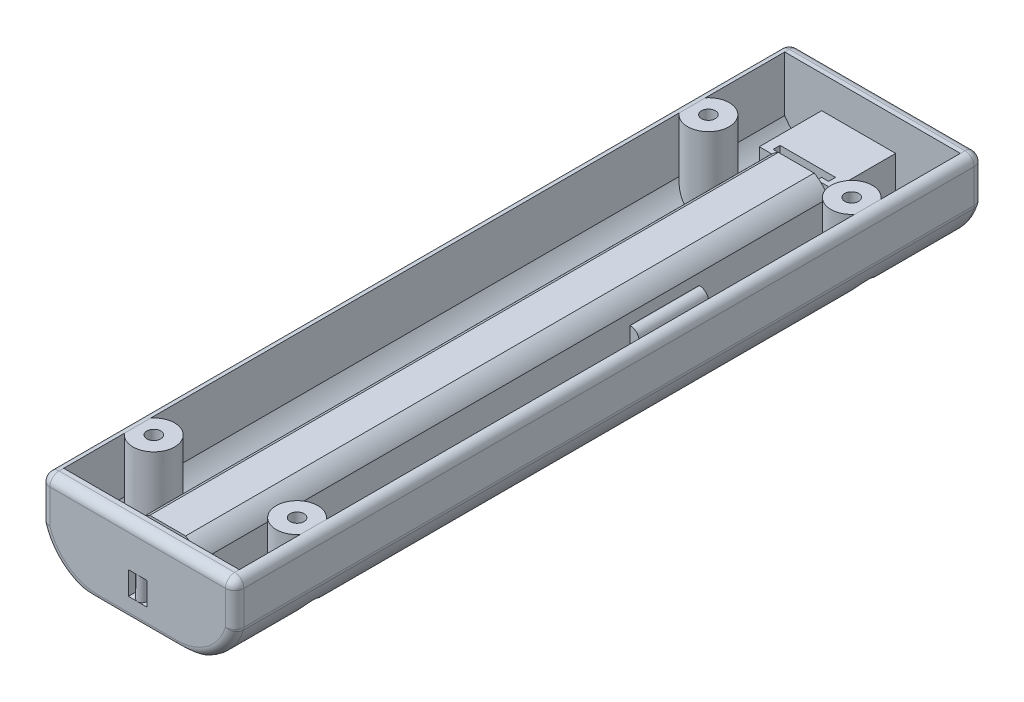
SolidWorks part; units mm, degrees
ref_plane "Alzado" through (0, 0, 0) normal (0, 0, 1) x (1, 0, 0)
ref_plane "Planta" through (0, 0, 0) normal (0, 1, 0) x (1, 0, 0)
ref_plane "Vista lateral" through (0, 0, 0) normal (1, 0, 0) x (0, 0, -1)
sketch "Croquis1" plane through (0, 0, 0) normal (0, 1, 0) x (1, 0, 0)
  line L1 (21, -81) -> (-21, -81)
  line L2 (21, -81) -> (21, 81)
  line L3 (21, 81) -> (-21, 81)
  line L4 (-21, -81) -> (-21, 81)
  line L5 (21, -81) -> (-21, 81) construction
  line L6 (21, 81) -> (-21, -81) construction
  point P0 (0, 0)
  dimension "D1" = 42
  dimension "D2" = 162
extrude "Saliente-Extruir1" add sketch "Croquis1" along normal blind 3 contours L4 L1 L2 L3 | L2 L1 L4 L3 region at (0, 0, 0)
sketch "Croquis2" plane through (0, 3, 0) normal (0, 1, 0) x (1, 0, 0)
  line L1 (21, -81) -> (-21, -81)
  line L2 (21, -81) -> (21, 81)
  line L3 (21, 81) -> (-21, 81)
  line L4 (-21, -81) -> (-21, 81)
  line L5 (21, -81) -> (-21, 81) construction
  line L6 (21, 81) -> (-21, -81) construction
  line L7 (19, -78) -> (-19, -78)
  line L8 (19, -78) -> (19, 78)
  line L9 (19, 78) -> (-19, 78)
  line L10 (-19, -78) -> (-19, 78)
  line L11 (19, -78) -> (-19, 78) construction
  line L12 (19, 78) -> (-19, -78) construction
  point P0 (0, 0)
  point P7 (0, 0)
  dimension "D1" = 156
  dimension "D2" = 38
extrude "Saliente-Extruir2" add sketch "Croquis2" along normal blind 16
sketch "Croquis3" plane through (0, 3, 0) normal (0, 1, 0) x (1, 0, 0)
  line L0 (-19, -78) -> (19, -78) construction
  line L1 (8, -78) -> (-8, -78)
  line L2 (8, -78) -> (8, -74.5)
  line L3 (-4.5, -74.5) -> (-8, -74.5)
  line L4 (-8, -78) -> (-8, -74.5)
  line L5 (-19, 78) -> (-19, -78) construction
  line L6 (-4.5, -74.5) -> (-4.5, -75.5)
  line L7 (-4.5, -75.5) -> (-6, -75.5)
  line L8 (-6, -75.5) -> (-6, -77)
  line L9 (-6, -77) -> (6, -77)
  line L10 (6, -77) -> (6, -75.5)
  line L11 (6, -75.5) -> (4.5, -75.5)
  line L12 (4.5, -75.5) -> (4.5, -74.5)
  line L13 (8, -74.5) -> (4.5, -74.5)
  line L14 (-19, -6.5) -> (19, -6.5) construction
  line L15 (-19, 78) -> (-19, -78) construction
  line L16 (19, -78) -> (19, 78) construction
  line L17 (8, 61.5) -> (4.5, 61.5)
  line L18 (4.5, 62.5) -> (4.5, 61.5)
  line L19 (6, 62.5) -> (4.5, 62.5)
  line L20 (6, 64) -> (6, 62.5)
  line L21 (-6, 64) -> (6, 64)
  line L22 (-6, 62.5) -> (-6, 64)
  line L23 (-4.5, 62.5) -> (-6, 62.5)
  line L24 (-4.5, 61.5) -> (-4.5, 62.5)
  line L25 (-8, 65) -> (-8, 61.5)
  line L26 (-4.5, 61.5) -> (-8, 61.5)
  line L27 (8, 65) -> (8, 61.5)
  line L28 (8, 65) -> (-8, 65)
  dimension "D1" = 16
  dimension "D2" = 12
  dimension "D3" = 1.5
  dimension "D4" = 1
  dimension "D5" = 1
  dimension "D6" = 11
  dimension "D7" = 9
  dimension "D8" = 68
extrude "Saliente-Extruir3" add sketch "Croquis3" along normal blind 12
sketch "Croquis4" plane through (0, 0, 74.5) normal (0, 0, -1) x (-1, 0, 0)
  line L0 (7, 12.873) -> (7, 3)
  line L1 (4.5, 3) -> (8, 3) construction
  line L2 (-7, 12.873) -> (-7, 3)
  line L3 (-8, 3) -> (-4.5, 3) construction
  line L4 (-6, 3) -> (6, 3) construction
  line L5 (4.5, 15) -> (4.5, 3) construction
  line L6 (-4.5, 15) -> (-4.5, 3) construction
  line L8 (7, 3) -> (7, 2.7212)
  line L9 (7, 2.7212) -> (-7, 2.7212)
  line L10 (-7, 2.7212) -> (-7, 3)
  circle A0 centre (0, 9) radius 6
  arc A1 (7, 12.873) -> (-7, 12.873) centre (0, 9) ccw
  dimension "D2" = 16
  dimension "D3" = 6
  dimension "D4" = 2.5
  dimension "D5" = 2.5
extrude "Saliente-Extruir4" add sketch "Croquis4" along normal blind 136
sketch "Croquis5" plane through (0, 3, 0) normal (0, 1, 0) x (1, 0, 0)
  line L0 (19, 78) -> (-19, 78) construction
  line L1 (-19, 78) -> (-19, -78) construction
  circle A0 centre (-15.5, 58) radius 4.5
  circle A1 centre (-15.5, -62) radius 4.5
  circle A2 centre (15.5, -62) radius 4.5
  circle A3 centre (15.5, 58) radius 4.5
  dimension "D1" = 9
  dimension "D2" = 20
  dimension "D3" = 3.5
  dimension "D4" = 2
  dimension "D5" = 2
extrude "Saliente-Extruir5" add sketch "Croquis5" along normal blind 16
sketch "Croquis6" plane through (0, 0, 81) normal (0, 0, 1) x (1, 0, 0)
  line L0 (0, -10.45) -> (0, 10.45) construction
  line L19 (21, 12.9679) -> (21, 12.9909)
  line L21 (-19, 19) -> (-19, 3) construction
  line L26 (14.1445, 0) -> (14.1445, 2.5948)
  line L27 (15.9123, 0) -> (14.1445, 0)
  line L28 (21, 7.0833) -> (21, 4.481)
  line L29 (19, 7.0833) -> (21, 7.0833)
  line L30 (-8, 15) -> (-8, 3) construction
  line L31 (-19, 7.0833) -> (-21, 7.0833)
  line L32 (-21, 19) -> (-21, 0) construction
  line L33 (-21, 7.0833) -> (-21, 4.481)
  line L34 (-15.9123, 0) -> (-14.1445, 0)
  line L35 (21, 0) -> (-21, 0) construction
  line L36 (-14.1445, 0) -> (-14.1445, 2.5948)
  arc A10 (-21, 4.481) -> (-15.9123, 0) centre (-8, 14.1123) ccw
  arc A11 (-19, 7.0833) -> (-14.1445, 2.5948) centre (-8, 14.1123) ccw
  arc A12 (19, 7.0833) -> (14.1445, 2.5948) centre (8, 14.1123) cw
  arc A13 (21, 4.481) -> (15.9123, 0) centre (8, 14.1123) cw
  point P1 (-8, 12.9679)
  point P7 (8, -0.0321)
  point P9 (-21, 12.9679)
  point P10 (-8, -0.0321)
  point P15 (-8, 1.9679)
  point P16 (8, 1.9679)
  line M7 (-21, 0) -> (21, 0)
  line M10 (-21, 19) -> (-21, 0)
extrude "Saliente-Extruir6" add sketch "Croquis6" against normal blind 162 contours A11 L31 A10 L36 M10 M7 | A12 L26 L27 A13 L28 L29 region at (-17.6965, 3.4092, 81)
sketch "Croquis7" plane through (0, 0, 81) normal (0, 0, 1) x (1, 0, 0)
  line L0 (-21.5, 13) -> (-22.8206, 13)
  line L5 (8.5, 0) -> (-8.5, 0)
  line L9 (-22.8206, 13) -> (-22.8206, -1.4161)
  line L10 (-22.8206, -1.4161) -> (22.8206, -1.4161)
  line L11 (22.8206, -1.4161) -> (22.8206, 13)
  line L12 (22.8206, 13) -> (21.5, 13)
  arc A2 (8.5, 0) -> (21.5, 13) centre (8.5, 13) ccw
  arc A3 (-8.5, 0) -> (-21.5, 13) centre (-8.5, 13) cw
  point P8 (21, 0)
  dimension "D1" = 13
extrude "Cortar-Extruir2" cut sketch "Croquis7" against normal blind 162
sketch "Croquis12" plane through (19, 0, 0) normal (-1, 0, 0) x (0, 0, 1)
  line L0 (-81, 19) -> (81, 19) construction
  line L1 (-26, 13) -> (-11, 13)
  line L2 (-26, 13) -> (-26, 15.5)
  line L3 (-26, 15.5) -> (-11, 15.5)
  line L4 (-11, 13) -> (-11, 15.5)
  line L6 (-78, 19) -> (-78, 7.0833) construction
  dimension "D1" = 3.5
  dimension "D2" = 2.5
  dimension "D3" = 15
  dimension "D4" = 52
extrude "Saliente-Extruir7" add sketch "Croquis12" along normal blind 4.5
sketch "Croquis14" plane through (0, 0, -11) normal (0, 0, 1) x (1, 0, 0)
  line L0 (14.5, 15.5) -> (19, 15.5) construction
  line L1 (14.5, 15.5) -> (16.5, 15.5)
  line L2 (14.5, 15.5) -> (14.5, 18)
  line L3 (14.5, 18) -> (14.6, 18)
  line L4 (16.5, 15.5) -> (16.5, 16.1)
  line L5 (14.5, 13) -> (14.5, 15.5) construction
  arc A0 (14.6, 18) -> (16.5, 16.1) centre (14.6, 16.1) cw
  point P6 (15.5, 15.5)
  dimension "D1" = 1.9
extrude "Saliente-Extruir9" add sketch "Croquis14" against normal blind 15
sketch "Croquis15" plane through (0, 0, 74.5) normal (0, 0, 1) x (1, 0, 0)
  line L1 (-9.0489, 16) -> (7.6872, 16)
  line L2 (-9.0489, 16) -> (-9.0489, 17.8889)
  line L3 (-9.0489, 17.8889) -> (7.6872, 17.8889)
  line L4 (7.6872, 16) -> (7.6872, 17.8889)
  arc A0 (4.5, 12.9686) -> (-4.5, 12.9686) centre (0, 9) ccw construction
  dimension "D1" = 7
extrude "Cortar-Extruir3" cut sketch "Croquis15" against normal blind 136
sketch "Croquis16" plane through (0, 0, 81) normal (0, 0, 1) x (1, 0, 0)
fillet "Redondeo1" radius 2 16 edges at (16.3288, 2.6217, -81) (0, 19, -81) (-16.3288, 2.6217, -81) (0, 0, -81) (-21, 14.2146, -81) (-21, 19, 0) (-21, 9.4293, 0) (21, 19, 0) (21, 14.2146, -81) (21, 9.4293, 0) (-21, 14.2146, 81) (0, 19, 81) (21, 14.2146, 81) (16.3288, 2.6217, 81) (0, 0, 81) (-16.3288, 2.6217, 81)
sketch "Croquis18" plane through (0, 0, -61.5) normal (0, 0, 1) x (1, 0, 0)
  line L0 (-6, 9) -> (6, 9)
  line L1 (-6, 9) -> (-6, -4.2497)
  line L2 (6, 9) -> (6, -4.2497)
  line L3 (-6, -4.2497) -> (6, -4.2497)
  arc A0 (-4.5, 12.9686) -> (-4.5, 5.0314) centre (0, 9) ccw construction
  arc A1 (4.5, 5.0314) -> (4.5, 12.9686) centre (0, 9) ccw construction
extrude "Cortar-Extruir4" cut sketch "Croquis18" along normal blind 136
sketch "Croquis19" plane through (0, 0, 74.5) normal (0, 0, -1) x (-1, 0, 0)
  line L0 (6, 15) -> (6, 3) construction
  line L1 (6, 4) -> (-6, 4)
  line L2 (6, 4) -> (6, 2)
  line L3 (6, 2) -> (-6, 2)
  line L4 (-6, 4) -> (-6, 2)
  line L5 (-6, 3) -> (6, 3) construction
  point P8 (6, 3)
  dimension "D1" = 0
  dimension "D2" = 1
  dimension "D3" = 12
  dimension "D4" = 2
extrude "Cortar-Extruir5" cut sketch "Croquis19" against normal blind 4
sketch "Croquis20" plane through (0, 0, 74.5) normal (0, 0, -1) x (-1, 0, 0)
  line L0 (-6, 0) -> (-6, 2) construction
  line L1 (-6, -0.5) -> (6, -0.5)
  line L2 (-6, -0.5) -> (-6, 3.5)
  line L3 (-6, 3.5) -> (6, 3.5)
  line L4 (6, -0.5) -> (6, 3.5)
  line L5 (6, 2) -> (6, 4) construction
  line L6 (6, 4) -> (-6, 4) construction
  dimension "D1" = 4
  dimension "D2" = 0.5
extrude "Cortar-Extruir7" cut sketch "Croquis20" along normal blind 149
sketch "Croquis21" plane through (0, 3, 0) normal (0, 1, 0) x (1, 0, 0)
  line L0 (8, 65) -> (-8, 65) construction
  line L1 (-8, 65) -> (8, 65)
  line L2 (-8, 65) -> (-8, 75)
  line L3 (-8, 75) -> (8, 75)
  line L4 (8, 65) -> (8, 75)
  line L5 (-8, 65) -> (-8, 61.5) construction
  dimension "D1" = 16
  dimension "D2" = 0
  dimension "D3" = 10
extrude "Saliente-Extruir10" add sketch "Croquis21" along normal blind 12
sketch "Croquis24" plane through (0, 0, -65) normal (0, 0, 1) x (1, 0, 0)
  line L1 (-6, 3) -> (6, 3)
  line L2 (-6, 3) -> (-6, 3.5)
  line L3 (-6, 3.5) -> (6, 3.5)
  line L4 (6, 3) -> (6, 3.5)
extrude "Saliente-Extruir11" add sketch "Croquis24" along normal blind 3.5
sketch "Croquis27" plane through (0, 0, 81) normal (0, 0, 1) x (1, 0, 0)
  line L0 (-8.5, 2) -> (8.5, 2) construction
  line L1 (-17.1925, -1.5364) -> (20.9362, -1.5364)
  line L2 (-17.1925, -1.5364) -> (-17.1925, 1.5)
  line L3 (-17.1925, 1.5) -> (20.9362, 1.5)
  line L4 (20.9362, -1.5364) -> (20.9362, 1.5)
  dimension "D1" = 0.5
extrude "Cortar-Extruir8" cut sketch "Croquis27" against normal blind 164
sketch "Croquis28" plane through (0, 3, 0) normal (0, -1, 0) x (-1, 0, 0)
  circle A0 centre (0, 70.5) radius 1.5
  dimension "D1" = 3
extrude "Cortar-Extruir9" cut sketch "Croquis28" against normal blind 10
sketch "Croquis29" plane through (0, 19, 0) normal (0, 1, 0) x (1, 0, 0)
  circle A0 centre (-15.5, -62) radius 3.5
  circle A1 centre (15.5, -62) radius 3.5
  circle A2 centre (15.5, 58) radius 3.5
  circle A3 centre (-15.5, 58) radius 3.5
  dimension "D1" = 2
  dimension "D2" = 2
extrude "Cortar-Extruir10" cut sketch "Croquis29" against normal blind 20
sketch "Croquis30" plane through (0, 19, 0) normal (0, 1, 0) x (1, 0, 0)
  circle A0 centre (-15.5, -62) radius 3.5
  circle A1 centre (-15.5, -62) radius 1.5
  circle A2 centre (15.5, -62) radius 3.5
  circle A3 centre (15.5, -62) radius 1.5
  circle A4 centre (15.5, 58) radius 3.5
  circle A5 centre (15.5, 58) radius 1.5
  circle A6 centre (-15.5, 58) radius 3.5
  circle A7 centre (-15.5, 58) radius 1.5
  dimension "D1" = 3
  dimension "D2" = 2
  dimension "D3" = 2
extrude "Saliente-Extruir12" add sketch "Croquis30" against normal blind 5
ref_plane "Plano1" through (0, 10, 0) normal (0, 1, 0) x (1, 0, 0)
sketch "Croquis32" plane through (0, 10, 0) normal (0, 1, 0) x (1, 0, 0)
  line L0 (-6, -77) -> (-6, -75.5) construction
  line L1 (19, -81) -> (-19, -81) construction
  line L3 (-2, -83) -> (2, -83)
  line L4 (-2, -83) -> (-2, -78)
  line L5 (-2, -78) -> (2, -78)
  line L6 (2, -83) -> (2, -78)
  circle A0 centre (0, -80) radius 1
  dimension "D1" = 2
  dimension "D2" = 6
  dimension "D3" = 1
  dimension "D4" = 5
  dimension "3.5mm" = 4
  dimension "D5" = 4
  dimension "D6" = 3
extrude "Cortar-Extruir11" cut sketch "Croquis32" against normal blind 5
